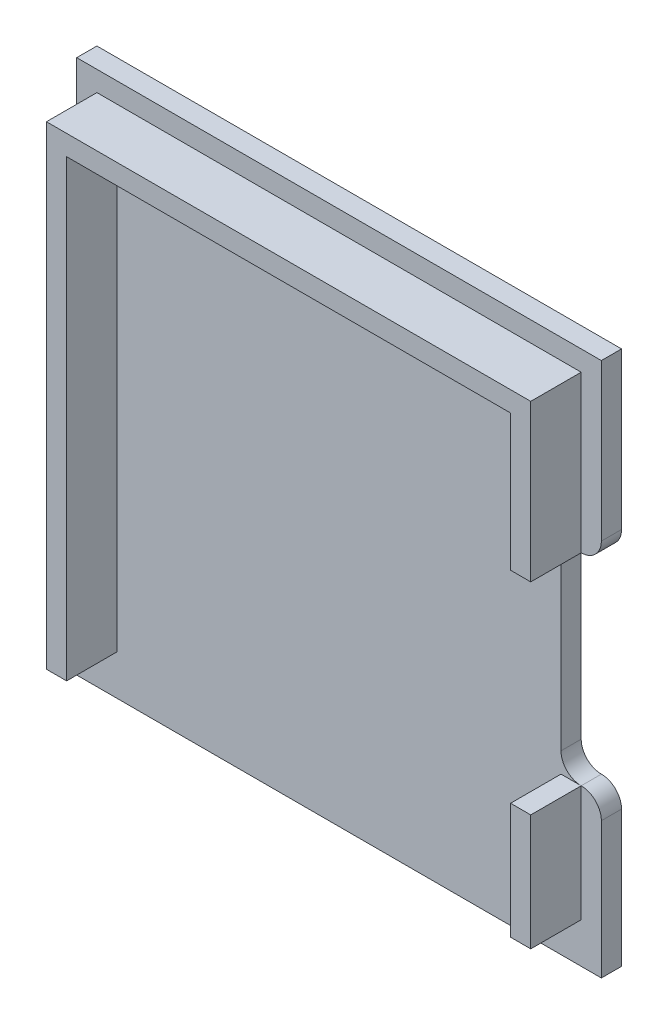
SolidWorks part; units mm, degrees
material "ABS"
ref_plane "Front Plane" through (0, 0, 0) normal (0, 0, 1) x (1, 0, 0)
ref_plane "Top Plane" through (0, 0, 0) normal (0, 1, 0) x (1, 0, 0)
ref_plane "Right Plane" through (0, 0, 0) normal (1, 0, 0) x (0, 0, -1)
sketch "Sketch1" plane through (0, 0, 0) normal (0, 0, 1) x (1, 0, 0)
  line L1 (0, 0) -> (52, 0)
  line L2 (0, 0) -> (0, 53)
  line L3 (0, 53) -> (52, 53)
  line L4 (52, 0) -> (52, 53)
  dimension "D1" = 52
  dimension "D2" = 53
extrude "Boss-Extrude1" add sketch "Sketch1" along normal blind 2
sketch "Sketch2" plane through (0, 0, 2) normal (0, 0, 1) x (1, 0, 0)
  line L0 (0, 53) -> (52, 0) construction
  line L1 (4, 4) -> (4, 49)
  line L2 (2, 2) -> (50, 2)
  line L3 (2, 2) -> (2, 51)
  line L4 (2, 51) -> (50, 51)
  line L5 (50, 2) -> (50, 51)
  line L6 (2, 2) -> (50, 51) construction
  line L7 (2, 51) -> (50, 2) construction
  line L8 (4, 49) -> (48, 49)
  line L9 (48, 4) -> (48, 49)
  line L10 (4, 4) -> (48, 4)
  point P2 (26, 26.5)
  dimension "D1" = 49
  dimension "D2" = 48
  dimension "D3" = 2
extrude "Boss-Extrude2" add sketch "Sketch2" along normal blind 5
sketch "Sketch3" plane through (0, 0, 0) normal (0, 0, -1) x (-1, 0, 0)
  line L0 (-52, 35.5) -> (-48, 35.5)
  line L1 (-52, 0) -> (-52, 53) construction
  line L2 (-48, 35.5) -> (-48, 15.5)
  line L3 (-48, 15.5) -> (-52, 15.5)
  line L4 (-52, 15.5) -> (-52, 35.5)
  line L5 (-52, 53) -> (0, 53) construction
  dimension "D1" = 17.5
  dimension "D2" = 20
  dimension "D3" = 4
extrude "Cut-Extrude1" cut sketch "Sketch3" against normal up to surface (7 mm away) up to face at (26, 26.5, 7)
fillet "Fillet1" radius 2 4 edges at (52, 15.5, 1) (48, 15.5, 1) (48, 35.5, 1) (52, 35.5, 1)
sketch "Sketch4" plane through (0, 0, 7) normal (0, 0, 1) x (1, 0, 0)
  line L0 (2, 51) -> (2, 2) construction
  line L1 (2, 4) -> (50, 4)
  line L2 (2, 4) -> (2, 2)
  line L3 (2, 2) -> (50, 2)
  line L4 (50, 4) -> (50, 2)
  line L5 (50, 2) -> (50, 15.5) construction
  line L6 (2, 2) -> (50, 2) construction
  line L7 (4, 4) -> (48, 4) construction
extrude "Cut-Extrude2" cut sketch "Sketch4" against normal up to surface (5 mm away) up to face at (39.5172, 25.9, 2)
